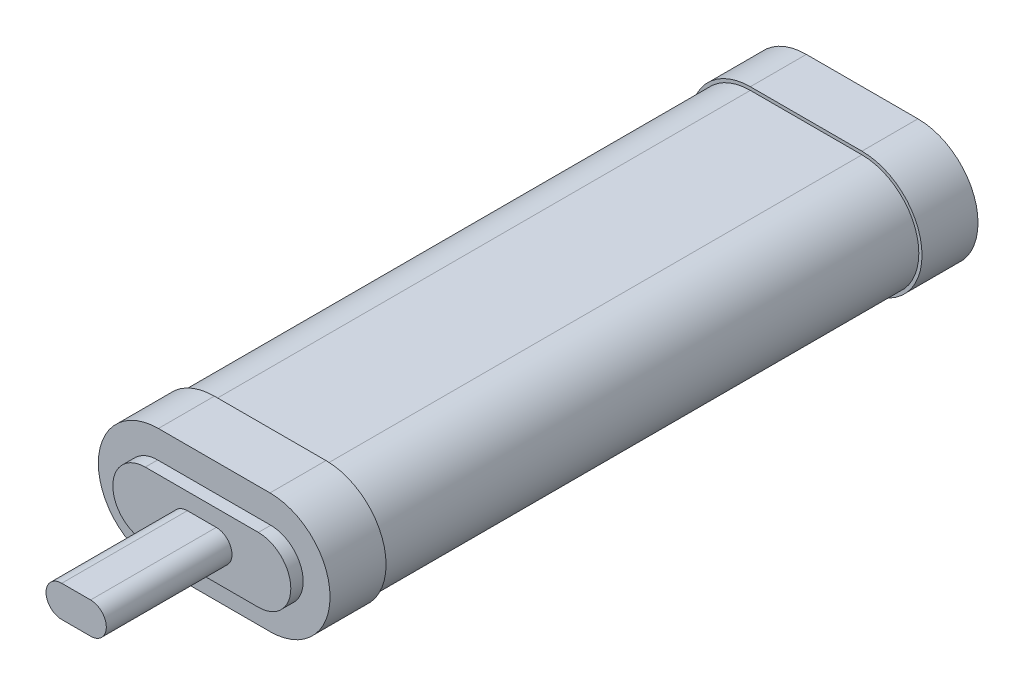
SolidWorks part; units mm, degrees
ref_plane "Front Plane" through (0, 0, 0) normal (0, 0, 1) x (1, 0, 0)
ref_plane "Top Plane" through (0, 0, 0) normal (0, 1, 0) x (1, 0, 0)
ref_plane "Right Plane" through (0, 0, 0) normal (1, 0, 0) x (0, 0, -1)
sketch "Sketch1" plane through (0, 0, 0) normal (0, 0, 1) x (1, 0, 0)
  line L0 (-11.1, 0) -> (11.1, 0) construction
  line L1 (-11.1, 11.315) -> (11.1, 11.315)
  line L2 (-11.1, -11.315) -> (11.1, -11.315)
  line L3 (-22.415, 0) -> (-22.415, 17.4549) construction
  line L4 (-22.415, 17.4549) -> (22.415, 17.4549) construction
  line L5 (22.415, 17.4549) -> (22.415, 0) construction
  arc A0 (-11.1, 11.315) -> (-11.1, -11.315) centre (-11.1, 0) ccw
  arc A1 (11.1, -11.315) -> (11.1, 11.315) centre (11.1, 0) ccw
  point P2 (0, 0)
  dimension "D1" = 22.63
  dimension "D2" = 44.83
extrude "Boss-Extrude1" add sketch "Sketch1" along normal mid plane 128.9
sketch "Sketch2" plane through (0, 0, 64.45) normal (0, 0, 1) x (1, 0, 0)
  line L4 (-11.1, -11.95) -> (11.1, -11.95)
  line L5 (11.1, 11.95) -> (-11.1, 11.95)
  line L6 (-11.1, -11.95) -> (11.1, -11.95)
  line L7 (11.1, 11.95) -> (-11.1, 11.95)
  arc A4 (-11.1, 11.95) -> (-11.1, -11.95) centre (-11.1, 0) ccw
  arc A5 (11.1, -11.95) -> (11.1, 11.95) centre (11.1, 0) ccw
  arc A6 (-11.1, 11.95) -> (-11.1, -11.95) centre (-11.1, 0) ccw
  arc A7 (11.1, -11.95) -> (11.1, 11.95) centre (11.1, 0) ccw
  dimension "D1" = 0.635
extrude "Boss-Extrude2" add sketch "Sketch2" against normal blind 11.14
mirror "Mirror1" about plane through (0, 0, 0) normal (0, 0, 1) of "Boss-Extrude2"
sketch "Sketch3" plane through (0, 0, 64.45) normal (0, 0, 1) x (1, 0, 0)
  line L0 (-11.25, 0) -> (11.25, 0) construction
  line L1 (-11.25, 6.45) -> (11.25, 6.45)
  line L2 (-11.25, -6.45) -> (11.25, -6.45)
  line L3 (-17.7, 0) -> (-17.7, 5.7399) construction
  line L4 (-17.7, 5.7399) -> (17.7, 5.7399) construction
  line L5 (17.7, 5.7399) -> (17.7, 0) construction
  arc A0 (-11.25, 6.45) -> (-11.25, -6.45) centre (-11.25, 0) ccw
  arc A1 (11.25, -6.45) -> (11.25, 6.45) centre (11.25, 0) ccw
  point P2 (0, 0)
  dimension "D1" = 35.4
  dimension "D2" = 12.9
extrude "Boss-Extrude3" add sketch "Sketch3" along normal offset from surface (2.46 mm away) 131.36 up to face at (0, 0, -64.45)
sketch "Sketch4" plane through (0, 0, 66.91) normal (0, 0, 1) x (1, 0, 0)
  line L0 (-2.875, 0) -> (2.875, 0) construction
  line L1 (-2.875, 3.125) -> (2.875, 3.125)
  line L2 (-2.875, -3.125) -> (2.875, -3.125)
  line L3 (-6, 0) -> (-6, 4.1768) construction
  line L4 (-6, 4.1768) -> (6, 4.1768) construction
  line L5 (6, 4.1768) -> (6, 0) construction
  arc A0 (-2.875, 3.125) -> (-2.875, -3.125) centre (-2.875, 0) ccw
  arc A1 (2.875, -3.125) -> (2.875, 3.125) centre (2.875, 0) ccw
  point P2 (0, 0)
  dimension "D1" = 6.25
  dimension "D2" = 12
extrude "Boss-Extrude4" add sketch "Sketch4" along normal blind 25
